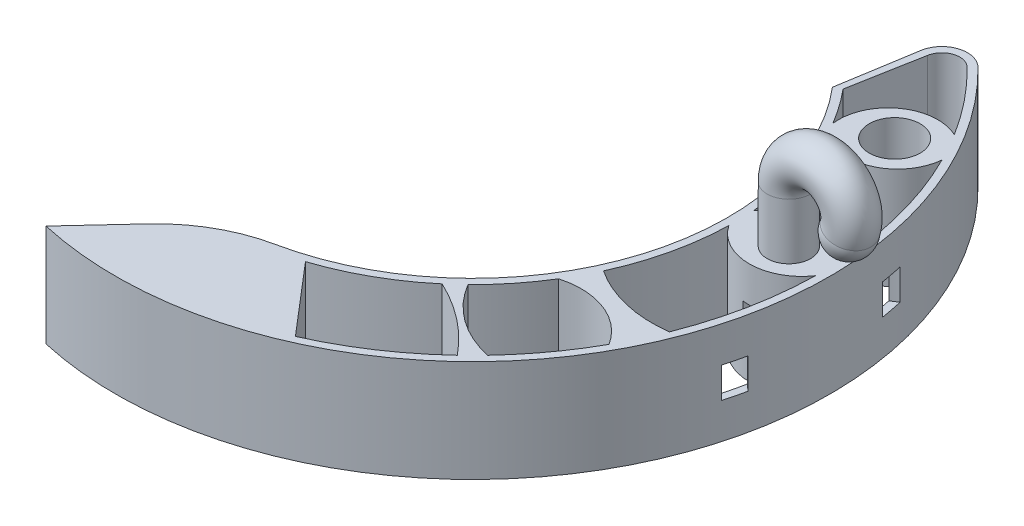
SolidWorks part; units mm, degrees
ref_plane "Front Plane" through (0, 0, 0) normal (0, 0, 1) x (1, 0, 0)
ref_plane "Top Plane" through (0, 0, 0) normal (0, 1, 0) x (1, 0, 0)
ref_plane "Right Plane" through (0, 0, 0) normal (1, 0, 0) x (0, 0, -1)
sketch "Sketch1" plane through (0, 0, 0) normal (0, 1, 0) x (1, 0, 0)
  line L0 (25.4386, 21.5353) -> (27.9933, 37.33)
  line L2 (1.1109, -33.3115) -> (-10.2169, -45.5277)
  arc A0 (25.4386, 21.5353) -> (1.1109, -33.3115) centre (0, 0) cw
  arc A1 (27.9933, 37.33) -> (-10.2169, -45.5277) centre (0, 0) cw
  dimension "D1" = 33.33
  dimension "D6" = 46.66
  dimension "D2" = 16
  dimension "D3" = 37.33
  dimension "D4" = 60
  dimension "D5" = 16.66
extrude "Boss-Extrude1" add sketch "Sketch1" along normal blind 13.33
fillet "Fillet1" radius 20 1 edges at (1.1109, 6.665, 33.3115)
sketch "Sketch2" plane through (0, 13.33, 0) normal (0, 1, 0) x (1, 0, 0)
  line L0 (-3.8058, -38.6138) -> (-3.8058, -39.2805)
  line L1 (-3.8058, -39.2805) -> (-4.4705, -39.3307)
  line L2 (-3.8058, -38.6138) -> (-10.2169, -45.5277) construction
  line L3 (-3.8058, -39.2805) -> (-4.1382, -38.9722) construction
  line L4 (-4.4705, -39.3307) -> (-3.8058, -38.6138)
  dimension "D1" = 0.6667
  dimension "D2" = 0.4533
extrude "Cut-Extrude1" [suppressed] cut sketch "Sketch2" against normal through all and the other way through all
pattern_linear "LPattern1" [suppressed] count 7 spacing 1.33 of bodies 102
sketch "Sketch3" plane through (0, 13.33, 0) normal (0, 1, 0) x (1, 0, 0)
  line L0 (29.1016, 16.2476) -> (40.6522, 22.9032) construction
  circle A0 centre (35.2891, 19.8129) radius 3.33
  arc A1 (6.787, -32.6317) -> (25.4386, 21.5353) centre (0, 0) ccw construction
  arc A2 (-10.2169, -45.5277) -> (27.9933, 37.33) centre (0, 0) ccw construction
  dimension "D1" = 6.66
  dimension "D2" = 10
extrude "Cut-Extrude2" cut sketch "Sketch3" against normal through all
fillet "Fillet2" radius 3.333 1 edges at (27.9933, 6.665, -37.33)
sketch "Sketch4" plane through (0, 13.33, 0) normal (0, 1, 0) x (1, 0, 0)
  circle A0 centre (40.567, 0.7155) radius 2.8333
  circle A1 centre (35.2891, 19.8129) radius 3.33 construction
  dimension "D1" = 5.6667
  dimension "D2" = 19.8133
  dimension "D3" = 40.5733
sketch "Sketch6" plane through (0, 0, 0) normal (0, 0, 1) x (1, 0, 0)
  line L0 (40.567, 13.33) -> (40.567, 20.6367)
  line L1 (43.4004, 13.33) -> (37.7337, 13.33) construction
  arc A0 (40.567, 20.6367) -> (48.567, 19.4146) centre (44.6604, 20.6367) cw
  dimension "D2" = 8
  dimension "D1" = 4.0933
  dimension "D3" = 7.3067
sweep "Sweep1" add profiles "Sketch4" path "Sketch6"
dome "Dome1" faces to dome 1 distance 3.3333 reverse direction no elliptical dome no face at (48.567, 19.4146, 2.1178) parameters "D1"=3.3333
ref_plane "Plane1" through (0, 6.665, 0) normal (0, 1, 0) x (1, 0, 0)
sketch "Sketch7" plane through (0, 6.665, 0) normal (0, 1, 0) x (1, 0, 0)
  arc A0 (44.9659, -12.459) -> (45.646, -9.6747) centre (0, 0) ccw
  arc A1 (-10.2169, -45.5277) -> (32.6689, 33.3151) centre (0, 0) ccw construction
  arc A2 (46.0579, 7.4718) -> (45.5122, 10.2856) centre (0, 0) ccw
  arc A3 (45.646, -9.6747) -> (46.0579, 7.4718) centre (52.1921, -1.2537) cw
  arc A4 (44.9659, -12.459) -> (45.5122, 10.2856) centre (52.1921, -1.2537) cw
  circle A5 centre (35.2891, 19.8129) radius 3.33 construction
  dimension "D1" = 10.666
  dimension "D2" = 13.3333
  dimension "D3" = 2.8667
  dimension "D4" = 21.0667
extrude "Cut-Extrude3" cut sketch "Sketch7" against normal mid plane 4
ref_plane "Plane3" through (-10.2169, 0, 45.5277) normal (-0.219, 0, 0.9757) x (0.9757, 0, 0.219)
sketch "Sketch10" plane through (0, 0, 0) normal (0, -1, 0) x (1, 0, 0)
  line L2 (-2.2542, 38.9234) -> (-9.2389, 45.7362)
  line L3 (-9.2389, 45.7362) -> (-10.2169, 45.5277)
  line L4 (6.787, 32.6317) -> (7.4727, 33.8523)
  line L5 (-9.2389, 45.7362) -> (17.4523, 45.7362) construction
  line L6 (7.4727, 33.8523) -> (-3.2128, 33.8523) construction
  line L22 (25.4386, -21.5353) -> (27.0451, -31.4676)
  line L23 (-10.2169, 45.5277) -> (-3.8058, 38.6138)
  line L45 (-10.2169, 45.5277) -> (-3.8058, 38.6138)
  arc A1 (32.6689, -33.3151) -> (-10.2169, 45.5277) centre (0, 0) ccw construction
  arc A2 (-3.8058, 38.6138) -> (6.787, 32.6317) centre (10.8595, 52.2126) ccw
  arc A3 (-2.2542, 38.9234) -> (7.4727, 33.8523) centre (10.8595, 52.2126) ccw
  arc A4 (27.0451, -31.4676) -> (32.6689, -33.3151) centre (30.3353, -30.9354) ccw
  arc A5 (32.6689, -33.3151) -> (-10.2169, 45.5277) centre (0, 0) ccw
  arc A6 (-3.8058, 38.6138) -> (6.787, 32.6317) centre (10.8595, 52.2126) ccw
  arc A7 (25.4386, -21.5353) -> (6.787, 32.6317) centre (0, 0) ccw
  dimension "D2" = 20
  dimension "D4" = 18.6701
  dimension "D3" = 1.4
  dimension "D5" = 9.757
  dimension "D6" = 1
  dimension "D7" = 44.286
  dimension "D11" = 1.5821
  dimension "D12" = 60.674
  dimension "D13" = 192.034
  dimension "D1" = 0
sketch "Sketch11" plane through (-10.2169, 0, 45.5277) normal (-0.219, 0, 0.9757) x (0.9757, 0, 0.219)
  line L0 (0, 0) -> (-0.144, -4.5)
  arc A0 (-0.144, -4.5) -> (-7.0098, -18.952) centre (-20.1338, -3.8603) cw
  dimension "D1" = 20
  dimension "D2" = 4.5
  dimension "D3" = 16
sweep "Sweep3" [suppressed] add profiles "Sketch10" path "Sketch11"
fillet "Fillet3" [suppressed] radius 3.3333
sketch "Sketch8" plane through (0, 0, 0) normal (0, -1, 0) x (1, 0, 0)
  arc A0 (22.7195, 25.9629) -> (4.3537, 34.2242) centre (0, 0) ccw
  arc A1 (25.3537, 28.9731) -> (-1.2031, 38.4812) centre (0, 0) ccw
  arc A2 (4.3537, 34.2242) -> (-1.2031, 38.4812) centre (7.3628, 43.9074) cw
  arc A3 (25.3537, 28.9731) -> (22.7195, 25.9629) centre (21.9954, 29.2542) cw
  dimension "D1" = 34.5
  dimension "D2" = 38.5
  dimension "D3" = 10.14
  dimension "D4" = 3.37
  dimension "D7" = 21
  dimension "D5" = 4
  dimension "D6" = 7
  dimension "D8" = 27
mirror "Mirror1" [suppressed] about plane through (0, 6.665, 0) normal (0, 1, 0)
sketch "Sketch15" [suppressed] plane through (0, 0, 0) normal (1, 0, 0) x (0, 0, -1)
  line L0 (-44.1567, 13.33) -> (-35.6752, 24.018)
rib "Rib2" [suppressed] sketch "Sketch15" sketch "Sketch15" thickness 3 extrusion direction parallel to sketch draft on no parameters "D1"=3
mirror "Mirror2" [suppressed] about plane through (0, 6.665, 0) normal (0, 1, 0)
fillet "Fillet6" [suppressed] radius 2
fillet "Fillet7" [suppressed] radius 2
fillet "Fillet9" [suppressed] radius 2
mirror "Mirror3" [suppressed] about plane through (0, 6.665, 0) normal (0, 1, 0)
sketch "Sketch16" [suppressed] plane through (0, 13.33, 0) normal (0, 1, 0) x (1, 0, 0)
  line L1 (60.3185, -9.5057) -> (23.5897, -9.5057)
  line L2 (60.3185, -9.5057) -> (60.3185, 9.5057)
  line L3 (60.3185, 9.5057) -> (23.5897, 9.5057)
  line L4 (23.5897, -9.5057) -> (23.5897, 9.5057)
  line L5 (60.3185, -9.5057) -> (23.5897, 9.5057) construction
  line L6 (60.3185, 9.5057) -> (23.5897, -9.5057) construction
  point P0 (41.9541, 0)
extrude "Cut-Extrude4" [suppressed] cut sketch "Sketch16" along normal blind 30
sketch "Sketch17" [suppressed] plane through (-9.7279, -0.016, 45.6319) normal (-0.2085, -0.0003, 0.978) x (0.978, -0.0001, 0.2085)
  line L0 (-0.5, 0.016) -> (-0.6437, -4.484) construction
  line L1 (-0.501, 13.346) -> (-0.5, 0.016) construction
  line L2 (-0.501, 13.346) -> (-0.6453, 17.846) construction
  line L3 (-0.5, 0.016) -> (-0.6437, -4.484)
  line L4 (-0.501, 13.346) -> (-0.5, 0.016)
  line L5 (-0.501, 13.346) -> (-0.6453, 17.846)
  line L6 (-7.5117, 32.2975) -> (-7.508, -18.9366)
  ellipse E0 centre (-20.6323, -3.8459) end of major axis (-21.2705, -23.8357) minor radius 19.9989 (-7.508, -18.9366) -> (-0.6437, -4.484) ccw construction
  ellipse E1 centre (-20.6339, 17.2047) end of major axis (-21.2721, -2.7851) minor radius 19.9989 (-0.6453, 17.846) -> (-7.5117, 32.2975) ccw construction
  ellipse E2 centre (-20.6323, -3.8459) end of major axis (-21.2705, -23.8357) minor radius 19.9989 (-7.508, -18.9366) -> (-0.6437, -4.484) ccw
  ellipse E3 centre (-20.6339, 17.2047) end of major axis (-19.9957, 37.1945) minor radius 19.9989 (-0.6453, 17.846) -> (-7.5117, 32.2975) ccw
extrude "Boss-Extrude2" [suppressed] add sketch "Sketch17" along normal blind 1 separate body
ref_axis "Axis1" [suppressed] through (21.9954, 0, 29.2542) along (0, -1, 0)
ref_plane "Plane2" [suppressed] through (8.1155, 0, -3.4448) normal (-0.9205, 0, 0.3907) x (0, -1, 0)
sketch "Sketch18" plane through (0, 0, 0) normal (0, -1, 0) x (1, 0, 0)
  line L0 (28.0391, -31.3529) -> (26.3411, -22.0158)
  line L1 (18.5503, 41.722) -> (10.7491, 32.6038)
  arc A0 (32.0149, -32.5559) -> (38.7606, -24.134) centre (0, 0) ccw
  arc A1 (26.3411, -22.0158) -> (29.5437, -17.4848) centre (0, 0) ccw
  arc A2 (32.0149, -32.5559) -> (28.0391, -31.3529) centre (30.3353, -30.9354) cw
  arc A3 (32.6689, -33.3151) -> (-10.2169, 45.5277) centre (0, 0) ccw construction
  arc A4 (25.4386, -21.5353) -> (6.787, 32.6317) centre (0, 0) ccw construction
  arc A5 (38.7606, -24.134) -> (29.5437, -17.4848) centre (35.9985, -18.2501) cw
  arc A6 (40.8206, -20.4576) -> (30.3945, -15.96) centre (34.354, -21.1149) ccw
  arc A7 (40.8206, -20.4576) -> (45.5738, -2.8036) centre (0, 0) ccw
  arc A8 (30.3945, -15.96) -> (34.2425, -2.4493) centre (0, 0) ccw
  arc A9 (45.5738, -2.8036) -> (34.2425, -2.4493) centre (40.0853, 3.0392) cw
  arc A10 (45.6516, 0.8763) -> (34.3188, 0.8763) centre (39.9852, -2.9825) ccw
  arc A11 (45.6516, 0.8763) -> (42.4626, 16.7859) centre (0, 0) ccw
  arc A12 (34.3188, 0.8763) -> (31.261, 14.188) centre (0, 0) ccw
  arc A13 (42.4626, 16.7859) -> (31.261, 14.188) centre (40.339, 0.4943) ccw
  arc A14 (39.9311, 22.1438) -> (29.2241, 18.014) centre (31.8168, 27.2364) cw
  arc A15 (39.9311, 22.1438) -> (33.2447, 31.299) centre (0, 0) ccw
  arc A16 (29.2241, 18.014) -> (23.9606, 24.5853) centre (0, 0) ccw
  arc A17 (23.9606, 24.5853) -> (33.2447, 31.299) centre (36.2392, 17.3819) cw
  arc A18 (31.261, 33.2804) -> (22.1886, 26.1957) centre (11.2277, 49.5831) cw
  arc A19 (31.261, 33.2804) -> (18.5503, 41.722) centre (0, 0) ccw
  arc A20 (22.1886, 26.1957) -> (10.7491, 32.6038) centre (0, 0) ccw
  dimension "D1" = 1
  dimension "D2" = 1
  dimension "D4" = 6.5
  dimension "D3" = 6.5
  dimension "D8" = 9.58
  dimension "D5" = 26
  dimension "D6" = 31
  dimension "D7" = 12
extrude "Cut-Extrude5" cut sketch "Sketch18" against normal blind 13.34
ref_plane "Plane4" through (15.6134, 0, 27.6471) normal (0.4917, 0, 0.8707) x (0.8707, 0, -0.4917)
sketch "Sketch19" plane through (15.6134, 0, 27.6471) normal (0.4917, 0, 0.8707) x (0.8707, 0, -0.4917)
  line L0 (-10.1366, 0) -> (-10.1366, 13.33) construction
  line L1 (-22.3018, 0) -> (-10.1366, 0) construction
  circle A0 centre (-14.1366, 6.665) radius 1.425
  dimension "D2" = 2.85
  dimension "D1" = 4
  dimension "D3" = 6.665
extrude "Cut-Extrude6" cut sketch "Sketch19" along normal mid plane 17.2
